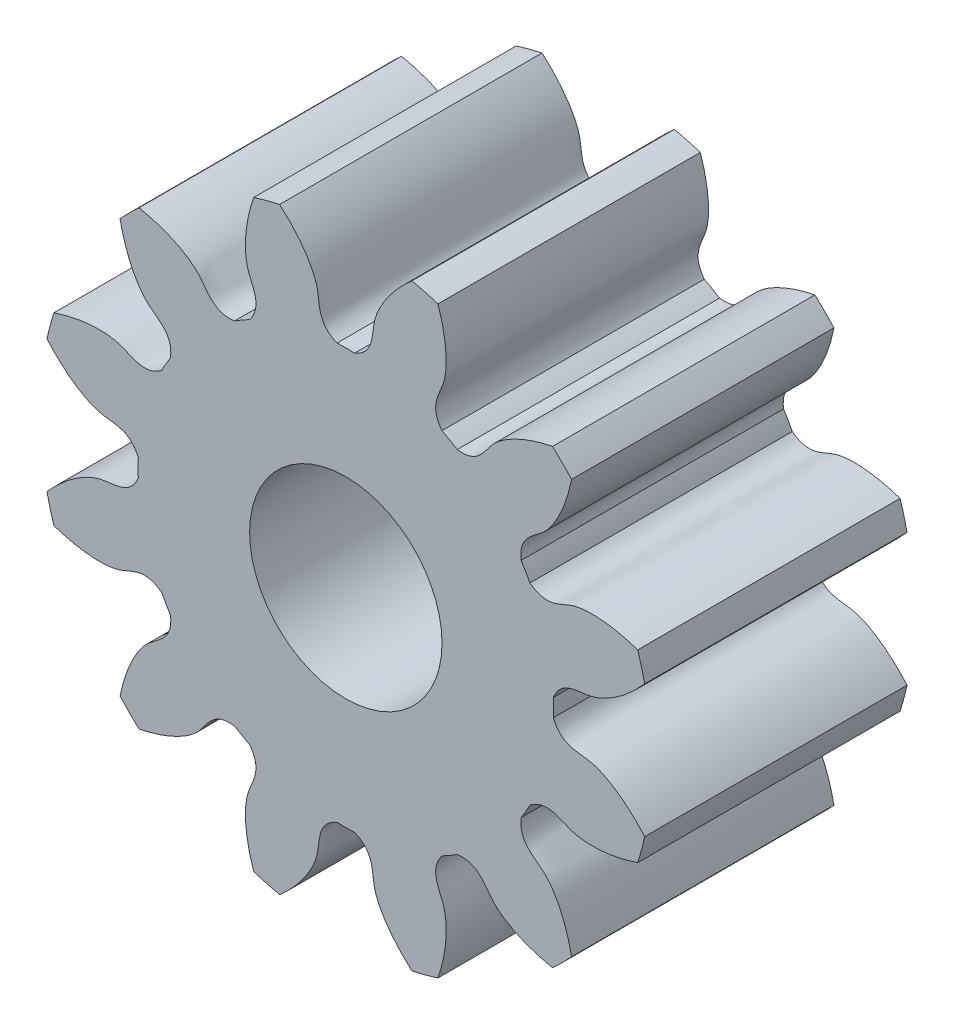
SolidWorks part; units mm, degrees
ref_plane "前视基准面" through (0, 0, 0) normal (0, 0, 1) x (1, 0, 0)
ref_plane "上视基准面" through (0, 0, 0) normal (0, 1, 0) x (1, 0, 0)
ref_plane "右视基准面" through (0, 0, 0) normal (1, 0, 0) x (0, 0, -1)
other "Configuration Table"
sketch "草图1" plane through (0, 0, 0) normal (0, 0, 1) x (1, 0, 0)
  circle A0 centre (0, 0) radius 3.5
extrude "凸台-拉伸1" add sketch "草图1" along normal blind 3
ref_axis "基准轴1" through (0, 0, 3) along (0, 0, -1)
sketch "草图2" plane through (0, 0, 0) normal (0, 0, 1) x (1, 0, 0)
  line L0 (0, 0) -> (0, 3.5) construction
  circle A0 centre (0, 0) radius 3.5 construction
  arc A1 (0.1004, 2.3729) -> (-0.1004, 2.3729) centre (0, 0) ccw
  arc A2 (1.7488, 3.9475) -> (-1.7488, 3.9475) centre (0, 0) ccw
  spline S0 degree 3 poles (0.1004, 2.3729) (0.3404, 2.4747) (0.2872, 2.6724) (0.3381, 2.8447) (0.3413, 2.855) (0.3451, 2.8662) (0.3495, 2.8784) (0.3546, 2.8915) (0.3603, 2.9056) (0.3668, 2.9206) (0.374, 2.9366) (0.3821, 2.9533) (0.3909, 2.971) (0.4007, 2.9894) (0.4114, 3.0086) (0.423, 3.0286) (0.4356, 3.0493) (0.4492, 3.0707) (0.4639, 3.0928) (0.4796, 3.1155) (0.4965, 3.1388) (0.5145, 3.1626) (0.5337, 3.187) (0.554, 3.2119) (0.5756, 3.2372) (0.5985, 3.2629) (0.6226, 3.289) (0.648, 3.3154) (0.6748, 3.342) (0.7028, 3.369) (0.7323, 3.3961) (0.7631, 3.4234) (0.7954, 3.4507) (0.829, 3.4782) (0.8641, 3.5057) (0.9006, 3.5331) (0.9385, 3.5604) (0.978, 3.5877) (1.0189, 3.6147) (1.0613, 3.6416) (1.1052, 3.6681) (1.1506, 3.6944) (1.1975, 3.7203) (1.2459, 3.7457) (1.2958, 3.7707) (1.3472, 3.7952) (1.4001, 3.8191) (1.4546, 3.8424) (1.5105, 3.865) (1.5679, 3.8869) (1.6472, 3.9154) (1.7078, 3.9351) (1.7488, 3.9475) knots 0 0 0 0 0.218015 0.222044 0.226546 0.231522 0.236972 0.242897 0.249295 0.256167 0.263513 0.271332 0.279626 0.288394 0.297636 0.307351 0.317541 0.328204 0.339341 0.350953 0.363038 0.375597 0.38863 0.402137 0.416118 0.430573 0.445502 0.460904 0.476781 0.493132 0.509956 0.527255 0.545027 0.563273 0.581994 0.601188 0.620856 0.640998 0.661614 0.682704 0.704268 0.726305 0.748817 0.771803 0.795262 0.819196 0.843603 0.868484 0.89384 0.919669 0.945972 1 1 1 1
  spline S1 degree 3 poles (-0.1004, 2.3729) (-0.3404, 2.4747) (-0.2872, 2.6724) (-0.3381, 2.8447) (-0.3413, 2.855) (-0.3451, 2.8662) (-0.3495, 2.8784) (-0.3546, 2.8915) (-0.3603, 2.9056) (-0.3668, 2.9206) (-0.374, 2.9366) (-0.3821, 2.9533) (-0.3909, 2.971) (-0.4007, 2.9894) (-0.4114, 3.0086) (-0.423, 3.0286) (-0.4356, 3.0493) (-0.4492, 3.0707) (-0.4639, 3.0928) (-0.4796, 3.1155) (-0.4965, 3.1388) (-0.5145, 3.1626) (-0.5337, 3.187) (-0.554, 3.2119) (-0.5756, 3.2372) (-0.5985, 3.2629) (-0.6226, 3.289) (-0.648, 3.3154) (-0.6748, 3.342) (-0.7028, 3.369) (-0.7323, 3.3961) (-0.7631, 3.4234) (-0.7954, 3.4507) (-0.829, 3.4782) (-0.8641, 3.5057) (-0.9006, 3.5331) (-0.9385, 3.5604) (-0.978, 3.5877) (-1.0189, 3.6147) (-1.0613, 3.6416) (-1.1052, 3.6681) (-1.1506, 3.6944) (-1.1975, 3.7203) (-1.2459, 3.7457) (-1.2958, 3.7707) (-1.3472, 3.7952) (-1.4001, 3.8191) (-1.4546, 3.8424) (-1.5105, 3.865) (-1.5679, 3.8869) (-1.6472, 3.9154) (-1.7078, 3.9351) (-1.7488, 3.9475) knots 0 0 0 0 0.218015 0.222044 0.226546 0.231522 0.236972 0.242897 0.249295 0.256167 0.263513 0.271332 0.279626 0.288394 0.297636 0.307351 0.317541 0.328204 0.339341 0.350953 0.363038 0.375597 0.38863 0.402137 0.416118 0.430573 0.445502 0.460904 0.476781 0.493132 0.509956 0.527255 0.545027 0.563273 0.581994 0.601188 0.620856 0.640998 0.661614 0.682704 0.704268 0.726305 0.748817 0.771803 0.795262 0.819196 0.843603 0.868484 0.89384 0.919669 0.945972 1 1 1 1
extrude "切除-拉伸1" cut sketch "草图2" along normal through all
pattern_circular "阵列(圆周)1" count 12 every 30 about axis through (0, 0, 3) along (0, 0, -1) of "切除-拉伸1"
sketch "草图3" plane through (0, 0, 0) normal (0, 0, 1) x (1, 0, 0)
  circle A0 centre (0, 0) radius 3 construction
  dimension "Dn" = 6
sketch "草图5" plane through (0, 0, 3) normal (0, 0, 1) x (1, 0, 0)
  circle A0 centre (0, 0) radius 1.1
  dimension "D1" = 2.2
extrude "切除-拉伸2" cut sketch "草图5" against normal up to next
